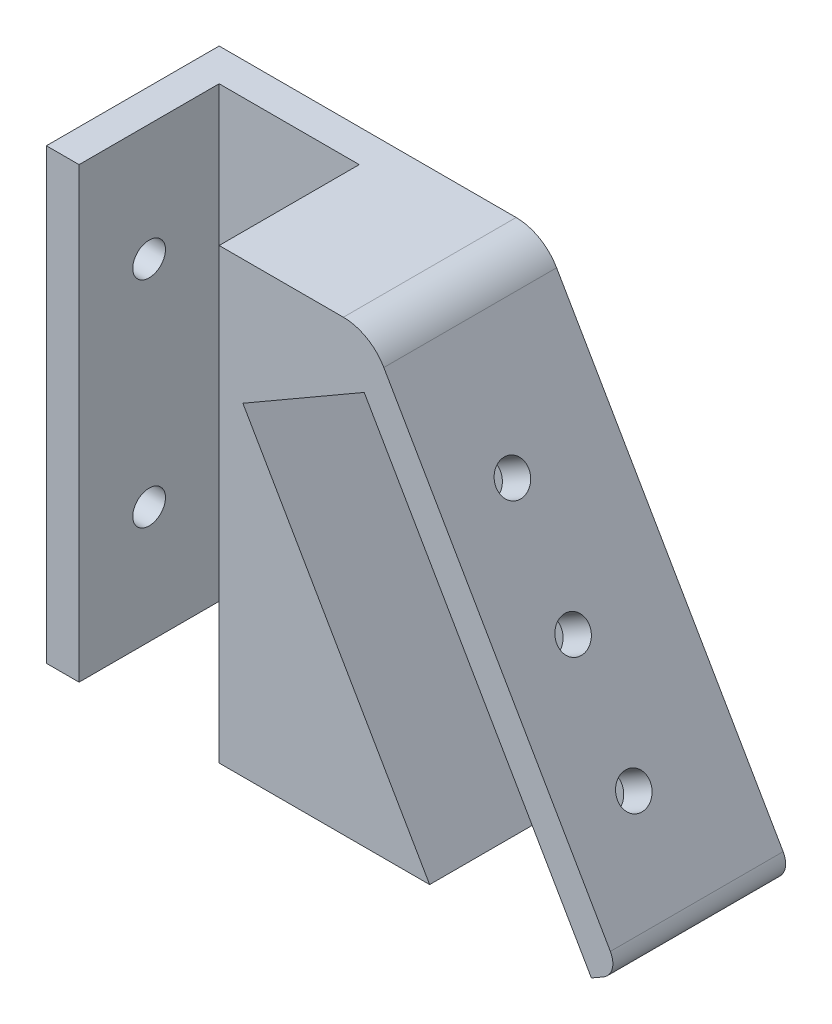
SolidWorks part; units mm, degrees
ref_plane "Front Plane" through (0, 0, 0) normal (0, 0, 1) x (1, 0, 0)
ref_plane "Top Plane" through (0, 0, 0) normal (0, 1, 0) x (1, 0, 0)
ref_plane "Right Plane" through (0, 0, 0) normal (1, 0, 0) x (0, 0, -1)
sketch "Sketch1" plane through (0, 0, 0) normal (0, 0, 1) x (1, 0, 0)
  line L0 (20.5456, 15.4888) -> (48.2584, -32.5112)
  line L2 (-14.145, 15.4888) -> (-14.145, -32.5112)
  line L3 (-14.145, -32.5112) -> (7.855, -32.5112)
  line L4 (7.855, 37.4696) -> (7.855, -32.5112) construction
  line L5 (48.2584, -32.5112) -> (7.855, -32.5112)
  line L6 (22.855, -32.5112) -> (7.855, -6.5304) construction
  line L7 (7.855, -6.5304) -> (45.9934, 15.4888) construction
  line L8 (20.5456, 15.4888) -> (-14.145, 15.4888)
  dimension "D2" = 30
  dimension "D3" = 22
  dimension "D4" = 30
  dimension "D5" = 48
extrude "Boss-Extrude1" add sketch "Sketch1" along normal blind 18.5
sketch "Sketch2" plane through (0, 0, 18.5) normal (0, 0, 1) x (1, 0, 0)
  line L1 (-14.145, -32.5112) -> (48.2584, -32.5112) construction
  line L2 (-10.645, 15.4888) -> (4.355, 15.4888)
  line L3 (-10.645, 15.4888) -> (-10.645, -32.5112)
  line L4 (-10.645, -32.5112) -> (4.355, -32.5112)
  line L5 (4.355, 15.4888) -> (4.355, -32.5112)
  line L6 (-14.145, 15.4888) -> (-14.145, -32.5112) construction
  line L7 (44.2169, -32.5112) -> (19.8868, 9.6298)
  line L8 (19.8868, 9.6298) -> (6.8964, 2.1298)
  line L9 (6.8964, 2.1298) -> (26.8964, -32.5112)
  line L10 (26.8964, -32.5112) -> (44.2169, -32.5112)
  line L11 (48.2584, -32.5112) -> (20.5456, 15.4888) construction
  line L12 (20.5456, 15.4888) -> (-14.145, 15.4888) construction
  dimension "D1" = 15
  dimension "D2" = 3.5
  dimension "D3" = 3.5
  dimension "D4" = 15
  dimension "D5" = 40
extrude "Cut-Extrude1" cut sketch "Sketch2" against normal offset from surface (15 mm away) 3.5 up to face at (10.1285, -8.5112, 0)
sketch "Sketch3" plane through (22.116, 12.7687, 0) normal (0.866, 0.5, 0) x (0, 0, -1)
  line L0 (-11, 30.2721) -> (-11, -52.2847) construction
  line L2 (-18.5, -52.2847) -> (0, -52.2847) construction
  circle A0 centre (-11, -38.2847) radius 1.75
  circle A1 centre (-11, -25.2847) radius 1.75
  circle A2 centre (-11, -12.2847) radius 1.75
  dimension "D1" = 3.5
  dimension "D2" = 14
  dimension "D4" = 13
  dimension "D3" = 13
extrude "Cut-Extrude2" cut sketch "Sketch3" against normal blind 3.5
sketch "Sketch4" plane through (0, 0, 0) normal (0, 0, -1) x (-1, 0, 0)
  line L0 (3.145, 15.4888) -> (3.145, -32.5112) construction
  line L2 (14.145, -32.5112) -> (-48.2584, -32.5112) construction
  line L3 (-13.3916, 5.8798) -> (-35.5567, -32.5112) construction
  line L4 (-6.8964, 2.1298) -> (-19.8868, 9.6298) construction
  line L5 (10.645, 15.4888) -> (-4.355, 15.4888) construction
  circle A0 centre (-30.5567, -23.851) radius 1.75
  circle A1 centre (-24.0567, -12.5926) radius 1.75
  circle A2 centre (-17.5567, -1.3343) radius 1.75
  circle A4 centre (3.145, 2.9888) radius 1.75
  circle A6 centre (3.145, -20.0112) radius 1.75
  circle A7 centre (3.145, 14.4888) radius 1.75 [skipped]
  circle A8 centre (3.145, -8.5112) radius 1.75 [skipped]
  dimension "D1" = 10
  dimension "D2" = 13
  dimension "D3" = 13
  dimension "D4" = 3.5
  dimension "D5" = 4
  dimension "D6" = 12.5
  dimension "D7" = 12.5
extrude "Cut-Extrude3" cut sketch "Sketch4" against normal blind 4
sketch "Sketch5" plane through (-14.145, 0, 0) normal (-1, 0, 0) x (0, 0, 1)
  line L0 (11, 15.4888) -> (11, -32.5112) construction
  line L2 (18.5, -32.5112) -> (0, -32.5112) construction
  line L3 (18.5, 15.4888) -> (18.5, -32.5112) construction
  line L4 (18.5, 15.4888) -> (0, 15.4888) construction
  circle A0 centre (11, -20.0112) radius 1.75
  circle A2 centre (11, 2.9888) radius 1.75
  circle A4 centre (11, 14.4888) radius 1.75 [skipped]
  circle A5 centre (11, -8.5112) radius 1.75 [skipped]
  dimension "D2" = 3.5
  dimension "D3" = 12.5
  dimension "D5" = 12.5
  dimension "D1" = 7.5
  dimension "D4" = 4
extrude "Cut-Extrude4" cut sketch "Sketch5" against normal blind 4
sketch "Sketch6" plane through (0, 0, 18.5) normal (0, 0, 1) x (1, 0, 0)
  line L0 (44.2169, -32.5112) -> (47.248, -30.7612)
  line L1 (48.2584, -32.5112) -> (20.5456, 15.4888) construction
  line L2 (47.248, -30.7612) -> (48.2584, -32.5112)
  line L3 (48.2584, -32.5112) -> (44.2169, -32.5112)
extrude "Cut-Extrude5" cut sketch "Sketch6" against normal blind 19
fillet "Fillet1" radius 2 1 edges at (47.248, -30.7612, 9.25)
fillet "Fillet2" radius 5 1 edges at (20.5456, 15.4888, 9.25)
